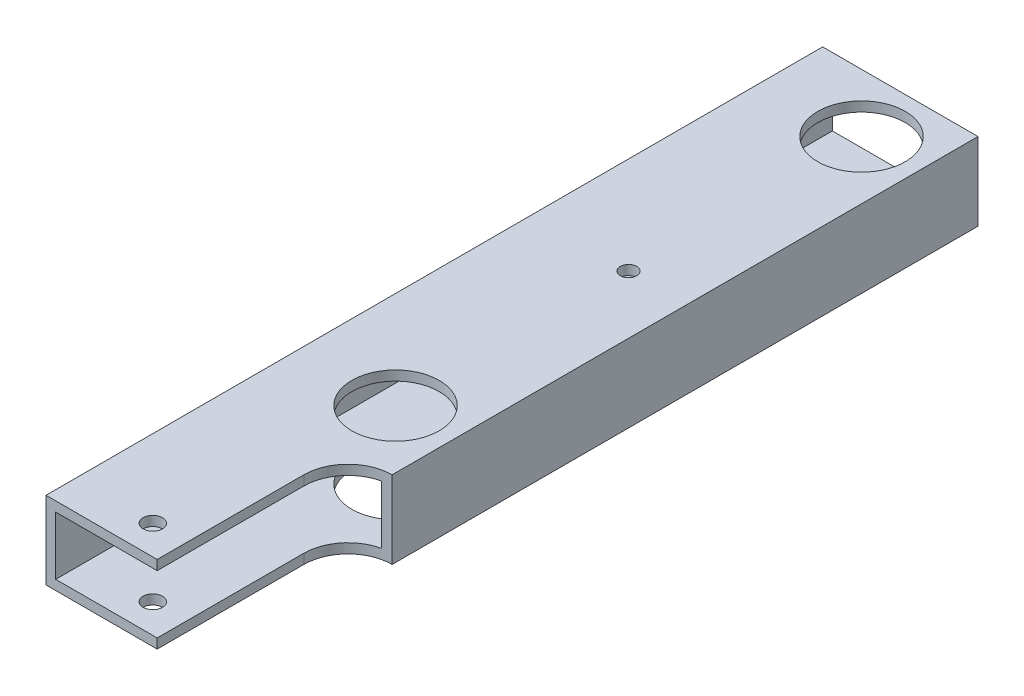
SolidWorks part; units mm, degrees
material "6063-T6"
ref_plane "Front" through (0, 0, 0) normal (0, 0, 1) x (1, 0, 0)
ref_plane "Top" through (0, 0, 0) normal (0, 1, 0) x (1, 0, 0)
ref_plane "Right" through (0, 0, 0) normal (1, 0, 0) x (0, 0, -1)
sketch "Sketch1" plane through (0, 0, 0) normal (0, 0, 1) x (1, 0, 0)
  line L0 (3.175, 3.175) -> (47.625, 3.175)
  line L1 (0, 0) -> (50.8, 0)
  line L2 (0, 0) -> (0, 25.4)
  line L3 (0, 25.4) -> (50.8, 25.4)
  line L4 (50.8, 0) -> (50.8, 25.4)
  line L5 (47.625, 3.175) -> (47.625, 22.225)
  line L6 (3.175, 22.225) -> (47.625, 22.225)
  line L7 (3.175, 3.175) -> (3.175, 22.225)
  dimension "D1" = 25.4
  dimension "D2" = 50.8
  dimension "D3" = 3.175
extrude "Boss-Extrude1" add sketch "Sketch1" along normal blind 254
sketch "Sketch2" plane through (0, 25.4, 0) normal (0, 1, 0) x (1, 0, 0)
  line L0 (31.75, 0) -> (31.75, -19.05) construction
  line L2 (31.75, -19.05) -> (31.75, -171.45) construction
  line L4 (50.8, -254) -> (50.8, 0) construction
  line L5 (50.8, 0) -> (0, 0) construction
  circle A0 centre (31.75, -19.05) radius 14.2875
  circle A1 centre (31.75, -171.45) radius 14.2875
  dimension "D1" = 28.575
  dimension "D4" = 28.575
  dimension "D2" = 19.05
  dimension "D3" = 152.4
  dimension "D5" = 19.05
extrude "Cut-Extrude1" cut sketch "Sketch2" against normal through all
sketch "Sketch3" plane through (0, 25.4, 0) normal (0, 1, 0) x (1, 0, 0)
  line L0 (25.4, -244.475) -> (25.4, -254) construction
  line L1 (50.8, -254) -> (0, -254) construction
  circle A0 centre (25.4, -244.475) radius 3.175
  dimension "D1" = 6.35
  dimension "D2" = 9.525
extrude "Cut-Extrude2" cut sketch "Sketch3" against normal through all
sketch "Sketch4" plane through (0, 25.4, 0) normal (0, 1, 0) x (1, 0, 0)
  line L0 (36.3589, -254) -> (36.3589, -206.0354)
  line L1 (50.8, -254) -> (0, -254) construction
  line L2 (50.8, -191.5943) -> (50.8, -254)
  line L3 (50.8, -254) -> (50.8, 0) construction
  line L4 (50.8, -254) -> (36.3589, -254)
  arc A0 (50.8, -191.5943) -> (36.3589, -206.0354) centre (50.8, -206.0354) ccw
extrude "Cut-Extrude3" cut sketch "Sketch4" against normal through all
sketch "Sketch5" plane through (0, 0, 0) normal (0, -1, 0) x (1, 0, 0)
  circle A0 centre (31.75, 95.25) radius 2.667 construction
  circle A1 centre (31.75, 95.25) radius 2.667
extrude "Cut-Extrude4" cut sketch "Sketch5" against normal through all
sketch "Sketch6" plane through (0, 0, 0) normal (0, 1, 0) x (1, 0, 0)
  circle A0 centre (31.75, -96.3958) radius 6.35
  dimension "D1" = 12.7
extrude "Cut-Extrude5" cut sketch "Sketch6" along normal up to next
